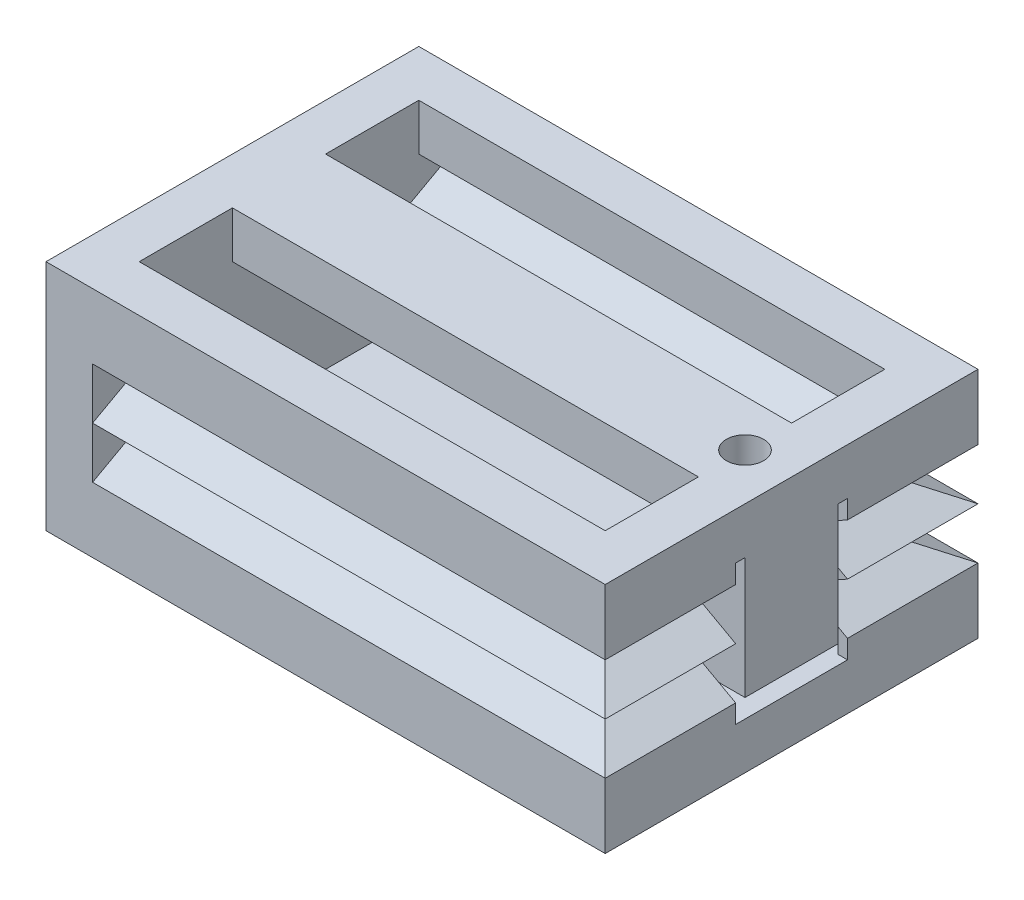
SolidWorks part; units mm, degrees
ref_plane "Front Plane" through (0, 0, 0) normal (0, 0, 1) x (1, 0, 0)
ref_plane "Top Plane" through (0, 0, 0) normal (0, 1, 0) x (1, 0, 0)
ref_plane "Right Plane" through (0, 0, 0) normal (1, 0, 0) x (0, 0, -1)
sketch "Sketch1" plane through (0, 0, 0) normal (0, 0, 1) x (1, 0, 0)
  line L0 (0, 0) -> (5.5, 0)
  line L1 (0, 0) -> (0, -1.5)
  line L2 (0, -1.5) -> (5.5, -1.5)
  line L3 (5.5, 0) -> (5.5, 0.5)
  line L4 (5.5, 0.5) -> (-0.5, 0.5)
  line L5 (-0.5, 0.5) -> (-0.5, -2)
  line L6 (-0.5, -2) -> (5.5, -2)
  line L7 (5.5, -2) -> (5.5, -1.5)
  dimension "D1" = 5.5
  dimension "D2" = 1.5
  dimension "D3" = 0.5
  dimension "D4" = 0.5
  dimension "0.5" = 0.5
extrude "Boss-Extrude1" add sketch "Sketch1" along normal blind 2 and the other way blind 2
sketch "Sketch2" plane through (0, 0.5, 0) normal (0, 1, 0) x (1, 0, 0)
  line L0 (5.5, -2) -> (5.5, 2) construction
  line L1 (4.5, -0.5) -> (5.5, -0.5)
  line L2 (4.5, -0.5) -> (4.5, 0.5)
  line L3 (4.5, 0.5) -> (5.5, 0.5)
  line L4 (5.5, -0.5) -> (5.5, 0.5)
  line L5 (4.5, -0.5) -> (5.5, 0.5) construction
  line L6 (4.5, 0.5) -> (5.5, -0.5) construction
  point P0 (5, 0)
  point P7 (5.5, 0)
  dimension "D1" = 1
extrude "Boss-Extrude2" add sketch "Sketch2" against normal blind 1.8
sketch "Sketch4" plane through (0, -1.3, 0) normal (0, -1, 0) x (1, 0, 0)
  line L0 (5.5, 0.5) -> (5.5, -0.5) construction
  line L1 (4.5, 0.5) -> (5.5, 0.5) construction
  circle A0 centre (5, 0) radius 0.2
  point P4 (5.5, 0)
  point P7 (5, 0.5)
  dimension "D1" = 0.4
extrude "Cut-Extrude1" cut sketch "Sketch4" against normal blind 11.5
sketch "Sketch5" plane through (0, 0.5, 0) normal (0, 1, 0) x (1, 0, 0)
  line L0 (-0.5, -2) -> (-0.5, 2) construction
  line L1 (0, 1.5) -> (5, 1.5)
  line L2 (0, 1.5) -> (0, 0.5)
  line L3 (0, 0.5) -> (5, 0.5)
  line L4 (5, 1.5) -> (5, 0.5)
  line L5 (0, -0.5) -> (5, -0.5)
  line L6 (0, -0.5) -> (0, -1.5)
  line L7 (0, -1.5) -> (5, -1.5)
  line L8 (5, -0.5) -> (5, -1.5)
  line L9 (5.5, -2) -> (5.5, 2) construction
  line L10 (5.5, 2) -> (-0.5, 2) construction
  line L11 (5.5, -2) -> (-0.5, -2) construction
  dimension "D1" = 0.5
  dimension "D2" = 0.5
  dimension "D3" = 0.5
  dimension "D4" = 0.5
  dimension "D5" = 1
extrude "Cut-Extrude2" cut sketch "Sketch5" against normal blind 1.5
sketch "Sketch6" plane through (0, -2, 0) normal (0, -1, 0) x (1, 0, 0)
  line L0 (5.5, 2) -> (5.5, -2) construction
  line L1 (3.1539, 0.75) -> (4.6539, 0.75)
  line L2 (3.1539, 0.75) -> (3.1539, -0.75)
  line L3 (3.1539, -0.75) -> (4.6539, -0.75)
  line L4 (4.6539, 0.75) -> (4.6539, -0.75)
  line L5 (3.1539, 0.75) -> (4.6539, -0.75) construction
  line L6 (3.1539, -0.75) -> (4.6539, 0.75) construction
  point P0 (3.9039, 0)
  point P7 (5.5, 0)
  dimension "D1" = 1.5
extrude "Cut-Extrude3" cut sketch "Sketch6" against normal blind 0.5
sketch "Sketch7" plane through (0, 0, 2) normal (0, 0, 1) x (1, 0, 0)
  line L0 (5.5, 0) -> (5.5, -0.2)
  line L1 (5.5, -1.3) -> (5.5, 0) construction
  line L3 (5.5, -1.5) -> (5.5, -1.3)
  line L5 (5.4, 0) -> (5.4, -0.1409)
  line L12 (5.5, -0.75) -> (5, -0.475)
  line L13 (5.5, -0.75) -> (5, -1.025)
  line L14 (5.4, -0.1409) -> (4.7925, -0.475)
  line L15 (5.2925, -0.75) -> (4.7925, -0.475)
  line L16 (5.2925, -0.75) -> (4.7925, -1.025)
  line L17 (5.5, -0.2) -> (5, -0.475)
  line L18 (5, -1.025) -> (5.5, -1.3)
  line L19 (4.7925, -1.025) -> (5.4, -1.3591)
  line L20 (5.4, -1.5) -> (5.4, -1.3591)
  line L21 (5.5, 0) -> (5.4, 0)
  line L22 (5.5, -1.5) -> (5.4, -1.5)
  dimension "D1" = 0.2
  dimension "D2" = 0.1
extrude "Boss-Extrude3" add sketch "Sketch7" against normal blind 1.4
sketch "Sketch8" plane through (5.5, 0, 0) normal (1, 0, 0) x (0, 0, -1)
  line L1 (-2, -0.2) -> (-2.0542, -0.75)
  line L4 (-2, -0.2) -> (-1.5, -0.475)
  line L5 (-0.6, -0.475) -> (-2, -0.475) construction
  line L6 (-1.5, -0.475) -> (-2, -0.75)
  line L7 (-2, -0.475) -> (-2, -0.2) construction
  line L9 (-2, -1.3) -> (-1.5, -1.025)
  line L10 (-0.6, -1.025) -> (-2, -1.025) construction
  line L11 (-1.5, -1.025) -> (-2, -0.75)
  line L12 (-2.0542, -0.75) -> (-2, -1.3)
  dimension "D1" = 0.5
extrude "Cut-Extrude4" cut sketch "Sketch8" against normal blind 1.4
sketch "Sketch9" plane through (5.5, 0, 0) normal (1, 0, 0) x (0, 0, -1)
  line L23 (-2, 0.5) -> (-2, -0.2)
  line L24 (-2, -0.2) -> (-1.5, -0.475)
  line L25 (-1.5, -0.475) -> (-2, -0.75)
  line L26 (-2, -0.75) -> (-1.5, -1.025)
  line L27 (-1.5, -1.025) -> (-2, -1.3)
  line L28 (-2, -1.3) -> (-2, -2)
  line L29 (-1.9, 0.5) -> (-1.9, -0.1409)
  line L30 (-1.9, -0.1409) -> (-1.2925, -0.475)
  line L31 (-1.2925, -0.475) -> (-1.7925, -0.75)
  line L32 (-1.7925, -0.75) -> (-1.2925, -1.025)
  line L33 (-1.2925, -1.025) -> (-1.9, -1.3591)
  line L34 (-1.9, -1.3591) -> (-1.9, -2)
  line L35 (-2, 0.5) -> (-1.9, 0.5)
  line L36 (-2, -2) -> (-1.9, -2)
  dimension "D1" = 0.1
extrude "Boss-Extrude4" add sketch "Sketch9" along normal up to next from surface starting at face at (0, -0.0833, 0)
mirror "Mirror1" about plane through (0, 0, 0) normal (0, 0, 1) of "Boss-Extrude3", "Cut-Extrude4", "Boss-Extrude4"
